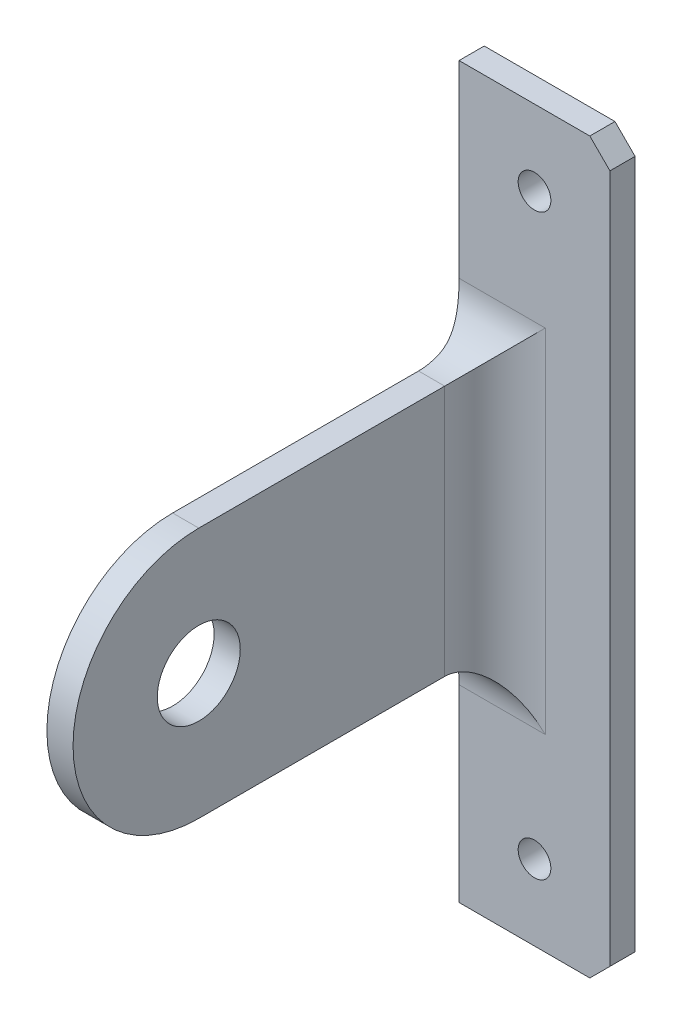
SolidWorks part; units mm, degrees
material "ABS"
ref_plane "Front Plane" through (0, 0, 0) normal (0, 0, 1) x (1, 0, 0)
ref_plane "Top Plane" through (0, 0, 0) normal (0, 1, 0) x (1, 0, 0)
ref_plane "Right Plane" through (0, 0, 0) normal (1, 0, 0) x (0, 0, -1)
sketch "Sketch1" plane through (0, 0, 0) normal (1, 0, 0) x (0, 0, -1)
  line L1 (0, 12.5) -> (34.45, 12.5)
  line L2 (0, 4.125) -> (0, -12.5)
  line L3 (0, -12.5) -> (34.45, -12.5)
  line L4 (34.45, 12.5) -> (34.45, -12.5)
  circle A0 centre (0, 0) radius 4.125
  circle A1 centre (0, 0) radius 12.5 construction
  arc A2 (0, 12.5) -> (0, -12.5) centre (0, 0) ccw
  dimension "D1" = 8.25
  dimension "D2" = 25
  dimension "D3" = 34.45
extrude "Boss-Extrude1" add sketch "Sketch1" along normal blind 2.6 contours L1 A2 A0 L3 L4 region at (0, 0, -12.849)
sketch "Sketch2" [suppressed] plane through (0, 0, 0) normal (-1, 0, 0) x (0, 0, 1)
  circle A0 centre (0, 0) radius 1.5
  circle A1 centre (0, 0) radius 4.5
  dimension "D1" = 9
  dimension "D2" = 3
sketch "Sketch4" [suppressed] plane through (2.5, 0, 0) normal (1, 0, 0) x (0, 0, -1)
  circle A0 centre (0, 0) radius 2.5
sketch "Sketch5" [suppressed] plane through (2.5, 0, 0) normal (1, 0, 0) x (0, 0, -1)
  circle A0 centre (0, 0) radius 4.5
  circle A1 centre (0, 0) radius 2.5
  dimension "D1" = 9
  dimension "D2" = 5
sketch "Sketch6" plane through (0, 0, -34.45) normal (0, 0, -1) x (-1, 0, 0)
  line L1 (-8.8125, 36.25) -> (53.3216, 36.25)
  line L3 (6.25, -36.25) -> (53.3216, -36.25)
  line L4 (53.3216, 36.25) -> (53.3216, -36.25)
  line L6 (53.3216, -36.25) -> (-19.1784, 36.25) construction
  line L7 (6.25, -36.25) -> (-19.1784, -36.25)
  line L9 (-8.8125, 36.25) -> (-19.1784, 36.25)
  line L10 (-19.1784, -36.25) -> (-19.1784, 36.25)
  line L11 (53.3216, 36.25) -> (-19.1784, -36.25) construction
  point P4 (17.0716, 0)
  dimension "D1" = 72.5
  dimension "D2" = 72.5
extrude "Boss-Extrude4" add sketch "Sketch6" against normal blind 2.5
ref_plane "Plane1" through (-17.0716, 0, 0) normal (1, 0, 0) x (0, 0, -1)
ref_plane "Plane2" through (9.4784, 0, 0) normal (1, 0, 0) x (0, 0, -1)
sketch "Sketch7" plane through (0, 0, -31.95) normal (0, 0, 1) x (1, 0, 0)
  line L7 (1.7881, -3.3824) -> (-5.2119, -3.3824)
  line L12 (1.7881, -3.3824) -> (1.7881, -19.8824)
  line L18 (1.7881, -19.8824) -> (-5.2119, -19.8824)
  line L19 (-5.2119, -3.3824) -> (-5.2119, -19.8824)
  line L20 (1.7881, -3.3824) -> (-5.2119, -19.8824) construction
  line L21 (1.7881, -19.8824) -> (-5.2119, -3.3824) construction
  line L22 (-24.5, -4) -> (-8.5, -4)
  line L23 (-24.5, -4) -> (-24.5, 4)
  line L24 (-24.5, 4) -> (-8.5, 4)
  line L25 (-8.5, -4) -> (-8.5, 4)
  line L26 (-24.5, -4) -> (-8.5, 4) construction
  line L27 (-24.5, 4) -> (-8.5, -4) construction
  point P0 (-16.5, 0)
  point P2 (-1.7119, -11.6324)
  dimension "D1" = 16
  dimension "D2" = 16.5
  dimension "D3" = 7
  dimension "D4" = 8
extrude "Cut-Extrude2" cut sketch "Sketch7" against normal up to next
sketch "Sketch8" plane through (0, 0, 0) normal (0, 1, 0) x (1, 0, 0)
  line L10 (2.6, 4.125) -> (0, 4.125)
  line L15 (2.6, 4.125) -> (2.6, 31.95)
  line L16 (2.6, 31.95) -> (0, 31.95)
  line L21 (0, 4.125) -> (0, 31.95)
sketch "Sketch9" plane through (0, -12.5, 0) normal (0, -1, 0) x (1, 0, 0)
  line L0 (2.6, 0) -> (2.6, -31.95) construction
  line L1 (0, -31.95) -> (2.6, -31.95)
  line L2 (0, -31.95) -> (0, -9.5612)
  line L3 (0, -9.5612) -> (2.6, -9.5612)
  line L4 (2.6, -31.95) -> (2.6, -9.5612)
extrude "Cut-Extrude3" cut sketch "Sketch9" against normal up to next
extrude "Boss-Extrude5" add sketch "Sketch8" along normal mid plane 25
fillet "Fillet1" [suppressed] radius 4
fillet "Fillet2" radius 1 8 edges at (-5.2119, -3.3824, -33.2) (-5.2119, -19.8824, -33.2) (1.7881, -3.3824, -33.2) (-8.5, 4, -33.2) (1.7881, -19.8824, -33.2) (-8.5, -4, -33.2) (-24.5, 4, -33.2) (-24.5, -4, -33.2)
fillet "Fillet3" radius 4 4 edges at (19.1784, -36.25, -33.2) (19.1784, 36.25, -33.2) (-53.3216, 36.25, -33.2) (-53.3216, -36.25, -33.2)
sketch "Sketch10" plane through (0, 0, 0) normal (0, 1, 0) x (1, 0, 0)
  line L0 (15.1784, 31.95) -> (19.1784, 31.95) construction
  line L1 (21.7259, 31.95) -> (-56.5098, 31.95)
  line L2 (21.7259, 31.95) -> (21.7259, 38.24)
  line L3 (21.7259, 38.24) -> (-56.5098, 38.24)
  line L4 (-56.5098, 31.95) -> (-56.5098, 38.24)
extrude "Cut-Extrude4" cut sketch "Sketch10" against normal through all both and the other way through all
sketch "Sketch11" plane through (0, 0, 0) normal (0, 1, 0) x (1, 0, 0)
  line L1 (14.03, 31.95) -> (-0.97, 31.95)
  line L2 (14.03, 31.95) -> (14.03, 29.45)
  line L3 (14.03, 29.45) -> (-0.97, 29.45)
  line L4 (-0.97, 31.95) -> (-0.97, 29.45)
  line L6 (2.6, 31.95) -> (0, 31.95) construction
  line L7 (0, 31.95) -> (0, 0) construction
  dimension "D1" = 2.5
  dimension "D2" = 15
  dimension "D3" = 0.97
extrude "Boss-Extrude6" add sketch "Sketch11" along normal mid plane 25
sketch "Sketch12" plane through (0, 0, -31.95) normal (0, 0, -1) x (-1, 0, 0)
  line L0 (24.4475, 0) -> (-24.4475, 0) construction
  line L1 (-14.03, 36.25) -> (58.47, 36.25) construction
  line L2 (-14.03, 36.25) -> (-14.03, -36.25) construction
  line L3 (-14.03, -36.25) -> (58.47, -36.25) construction
  line L4 (58.47, 36.25) -> (58.47, -36.25) construction
  line L5 (-14.03, 36.25) -> (58.47, -36.25) construction
  line L6 (58.47, 36.25) -> (-14.03, -36.25) construction
  line L7 (-14.03, 12.5) -> (-14.03, -12.5) construction
  circle A0 centre (-6.53, 28.75) radius 1.5
  circle A1 centre (-6.53, -28.75) radius 1.5
  circle A2 centre (-6.53, 28.75) radius 3
  circle A3 centre (-6.53, -28.75) radius 3
  point P4 (-14.03, 0)
  dimension "D3" = 3
  dimension "D5" = 6
  dimension "D1" = 72.5
  dimension "D2" = 72.5
  dimension "D4" = 7.5
sketch "Sketch13" plane through (0, 0, -31.95) normal (0, 0, -1) x (-1, 0, 0)
  line L0 (-14.03, 12.5) -> (0.97, 12.5) construction
  line L1 (-14.03, 12.5) -> (0.97, 12.5)
  line L2 (-14.03, 12.5) -> (-14.03, 32.25)
  line L4 (0.97, 12.5) -> (0.97, 36.25)
  line L5 (0.97, 36.25) -> (-10.03, 36.25)
  line L6 (-14.03, 32.25) -> (-14.03, 36.25)
  line L7 (-14.03, 36.25) -> (-10.03, 36.25)
  dimension "D1" = 4
  dimension "D3" = 15
  dimension "D4" = 36.25
  dimension "D5" = 4
extrude "Boss-Extrude7" add sketch "Sketch13" against normal blind 2.5
mirror "Mirror1" about plane through (0, 0, 0) normal (0, 1, 0) of "Boss-Extrude6", "Boss-Extrude7"
sketch "Sketch14" plane through (0, 0, -31.95) normal (0, 0, -1) x (-1, 0, 0)
  line L1 (0.97, -36.25) -> (0.97, 36.25) construction
  line L2 (0.97, 36.25) -> (-14.03, 36.25) construction
  circle A0 centre (-6.53, 28.75) radius 1.625
  dimension "D3" = 3.25
  dimension "D1" = 7.5
  dimension "D2" = 7.5
extrude "Cut-Extrude5" cut sketch "Sketch14" against normal blind 2.5
sketch "Sketch15" [suppressed] plane through (0, 0, -31.95) normal (0, 0, -1) x (-1, 0, 0)
  circle A0 centre (-6.53, 28.75) radius 2.5
  circle A1 centre (-6.53, 28.75) radius 4
  dimension "D1" = 8
  dimension "D2" = 5
extrude "Boss-Extrude8" [suppressed] add sketch "Sketch15" against normal blind 6
mirror "Mirror2" about plane through (0, 0, 0) normal (0, 1, 0) of "Cut-Extrude5", "Boss-Extrude8"
fillet "Fillet4" radius 5 4 edges at (1.3, -12.5, -29.45) (0, 0, -29.45) (1.3, 12.5, -29.45) (2.6, 0, -29.45)
chamfer "Chamfer1" distance 2 angle 45 2 edges at (14.03, -36.25, -30.7) (14.03, 36.25, -30.7)
sketch "Sketch16" plane through (2.6, 0, 0) normal (1, 0, 0) x (0, 0, -1)
  line L0 (0, 12.5) -> (0, 10.5)
  line L1 (0, -10.5) -> (0, -12.5)
  arc A0 (0, 12.5) -> (0, -12.5) centre (0, 0) ccw
  arc A1 (0, 10.5) -> (0, -10.5) centre (0, 0) ccw
  dimension "D1" = 2
extrude "Boss-Extrude9" [suppressed] add sketch "Sketch16" along normal blind 9.5
